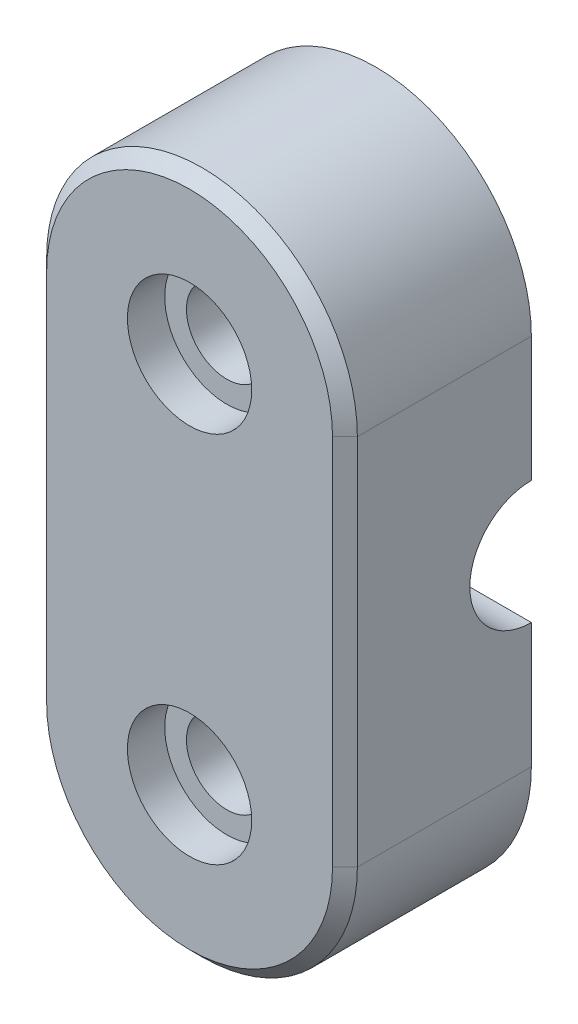
SolidWorks part; units mm, degrees
ref_plane "Front Plane" through (0, 0, 0) normal (0, 0, 1) x (1, 0, 0)
ref_plane "Top Plane" through (0, 0, 0) normal (0, 1, 0) x (1, 0, 0)
ref_plane "Right Plane" through (0, 0, 0) normal (1, 0, 0) x (0, 0, -1)
sketch "Sketch1" plane through (0, 0, 0) normal (0, 0, 1) x (1, 0, 0)
  line L0 (-12.5, 4.95) -> (12.5, 4.95) construction
  line L1 (12.5, 4.95) -> (12.5, 15) construction
  line L2 (-12.5, 15) -> (-12.5, 4.95) construction
  line L3 (12.5, -4.95) -> (-12.5, -4.95) construction
  line L4 (-12.5, -4.95) -> (-12.5, -15) construction
  line L5 (12.5, -15) -> (12.5, -4.95) construction
  line L6 (-12.5, 4.95) -> (12.5, 4.95)
  line L7 (12.5, 4.95) -> (12.5, 15)
  line L8 (-12.5, 15) -> (-12.5, 4.95)
  line L9 (12.5, -4.95) -> (-12.5, -4.95)
  line L10 (-12.5, -4.95) -> (-12.5, -15)
  line L11 (12.5, -15) -> (12.5, -4.95)
  line L12 (-12.5, -4.95) -> (-12.5, 4.95)
  line L13 (12.5, -4.95) -> (12.5, 4.95)
  arc A0 (12.5, 15) -> (-12.5, 15) centre (0, 15) ccw construction
  arc A1 (-12.5, -15) -> (12.5, -15) centre (0, -15) ccw construction
  arc A2 (12.5, 15) -> (-12.5, 15) centre (0, 15) ccw
  arc A3 (-12.5, -15) -> (12.5, -15) centre (0, -15) ccw
  circle A4 centre (0, 15) radius 3.25 construction
  circle A5 centre (0, -15) radius 3.25 construction
  circle A6 centre (0, 15) radius 3.25
  circle A7 centre (0, -15) radius 3.25
extrude "Boss-Extrude1" add sketch "Sketch1" along normal blind 15 contours L10 A3 L11 L9 A7 | L9 L13 L6 L12 | L7 A2 L8 L6 A6 region at (-12.1633, 9.975, 0) region at (0, 0, 0) region at (0, -5.2867, 0)
sketch "Sketch2" plane through (12.5, 0, 0) normal (1, 0, 0) x (0, 0, -1)
  circle A0 centre (0, 0) radius 4.95
  arc A1 (0, -4.95) -> (0, 4.95) centre (0, 0) ccw construction
extrude "Cut-Extrude1" cut sketch "Sketch2" against normal up to next
chamfer "Chamfer1" distance 1 angle 45 4 edges at (-12.5, 0, 15) (0, -27.5, 15) (0, 27.5, 15) (12.5, 0, 15)
sketch "Sketch3" plane through (0, 0, 15) normal (0, 0, 1) x (1, 0, 0)
  circle A0 centre (0, 15) radius 5
  circle A1 centre (0, -15) radius 5
  dimension "D1" = 10
extrude "Cut-Extrude2" cut sketch "Sketch3" against normal blind 3
